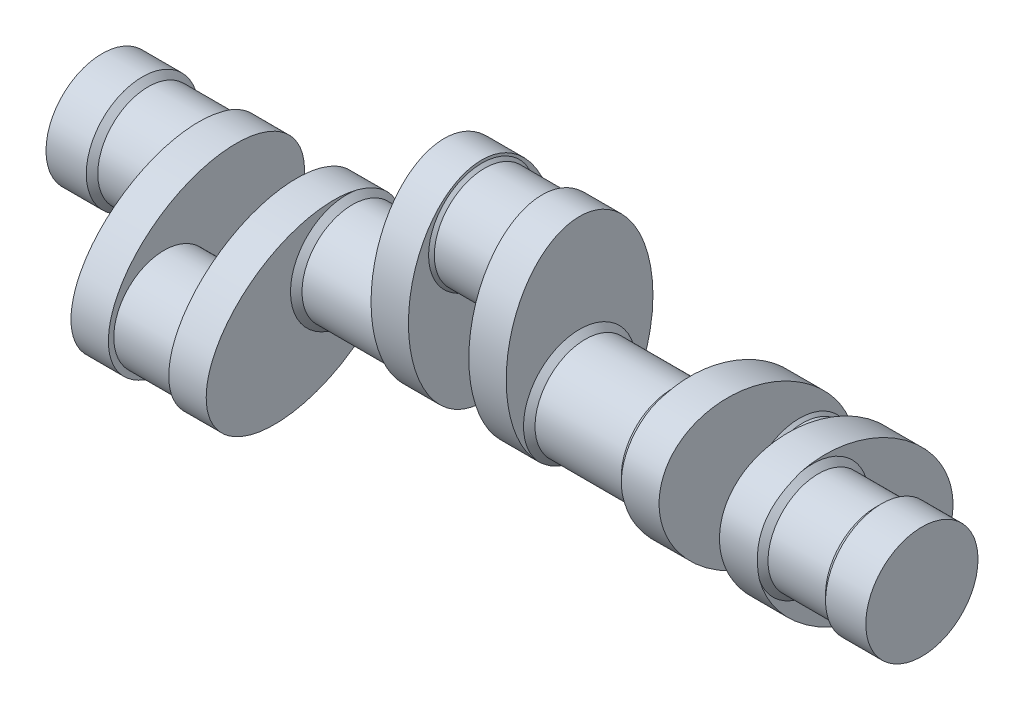
SolidWorks part; units mm, degrees
material "AISI 304"
ref_plane "Front Plane" through (0, 0, 0) normal (0, 0, 1) x (1, 0, 0)
ref_plane "Top Plane" through (0, 0, 0) normal (0, 1, 0) x (1, 0, 0)
ref_plane "Right Plane" through (0, 0, 0) normal (1, 0, 0) x (0, 0, -1)
sketch "Sketch1" plane through (0, 0, 0) normal (1, 0, 0) x (0, 0, -1)
  line L0 (0, 0) -> (0, -17) construction
  ellipse E0 centre (0, -17) end of major axis (0, -53.5) minor radius 25.5
extrude "Boss-Extrude1" add sketch "Sketch1" along normal blind 13
sketch "Sketch2" plane through (13, 0, 0) normal (1, 0, 0) x (0, 0, -1)
  circle A0 centre (0, 0) radius 17.5
  dimension "D1" = 35
extrude "Boss-Extrude2" add sketch "Sketch2" along normal blind 21
chamfer "Chamfer1" distance 1 angle 45 1 edges at (13, 0, -17.5)
sketch "Sketch3" plane through (34, 0, 0) normal (1, 0, 0) x (0, 0, -1)
  line L0 (0, 0) -> (0, -17) construction
  ellipse E0 centre (0, -17) end of major axis (0, -53.5) minor radius 25.5
extrude "Boss-Extrude3" add sketch "Sketch3" along normal blind 13
chamfer "Chamfer2" distance 1 angle 45 1 edges at (34, 0, -17.5)
sketch "Sketch5" plane through (47, 0, 0) normal (1, 0, 0) x (0, 0, -1)
  line L0 (0, 0) -> (0, -34) construction
  circle A0 centre (0, -34) radius 17.5
extrude "Boss-Extrude4" add sketch "Sketch5" along normal blind 34
chamfer "Chamfer3" distance 2 angle 45 1 edges at (47, -34, -17.5)
sketch "Sketch6" plane through (81, 0, 0) normal (1, 0, 0) x (0, 0, -1)
  line L0 (0, -34) -> (14.7224, -42.5) construction
  line L1 (0, -34) -> (0, 0) construction
  line L2 (27.4724, -20.4164) -> (14.7224, -42.5) construction
  ellipse E0 centre (14.7224, -42.5) end of major axis (46.3324, -60.75) minor radius 25.5
  dimension "D1" = 17
  dimension "D2" = 120
  dimension "D3" = 25.5
  dimension "D4" = 36.5
extrude "Boss-Extrude5" add sketch "Sketch6" along normal blind 13
chamfer "Chamfer4" distance 2 angle 45 1 edges at (81, -34, -17.5)
sketch "Sketch7" plane through (94, 0, 0) normal (1, 0, 0) x (0, 0, -1)
  line L0 (0, 0) -> (0, -34) construction
  line L1 (0, -34) -> (29.4449, -51) construction
  circle A0 centre (29.4449, -51) radius 17.5
  dimension "D1" = 120
  dimension "D2" = 34
extrude "Boss-Extrude6" add sketch "Sketch7" along normal blind 21
chamfer "Chamfer5" distance 1 angle 45 1 edges at (94, -51, -46.9449)
sketch "Sketch8" plane through (115, 0, 0) normal (1, 0, 0) x (0, 0, -1)
  line L0 (29.4449, -51) -> (14.7224, -42.5) construction
  line L1 (29.4449, -51) -> (29.4449, -68) construction
  line L2 (14.7224, -42.5) -> (1.9724, -64.5836) construction
  line L3 (14.7224, -42.5) -> (-16.8875, -24.25) construction
  ellipse E0 centre (14.7224, -42.5) end of major axis (-16.8875, -24.25) minor radius 25.5
  dimension "D1" = 120
  dimension "D2" = 25.5
  dimension "D3" = 17
  dimension "D4" = 36.5
extrude "Boss-Extrude7" add sketch "Sketch8" along normal blind 13
chamfer "Chamfer6" distance 1 angle 45 1 edges at (115, -51, -46.9449)
sketch "Sketch9" plane through (128, 0, 0) normal (1, 0, 0) x (0, 0, -1)
  line L0 (0, 0) -> (0, -34) construction
  circle A0 centre (0, -34) radius 17.5
  dimension "D1" = 35
  dimension "D2" = 34
extrude "Boss-Extrude8" add sketch "Sketch9" along normal blind 24
sketch "Sketch10" plane through (152, 0, 0) normal (1, 0, 0) x (0, 0, -1)
  circle A0 centre (0, -34) radius 19.5
  dimension "D1" = 39
extrude "Boss-Extrude9" add sketch "Sketch10" along normal blind 14
chamfer "Chamfer7" distance 2 angle 45 1 edges at (128, -34, -17.5)
chamfer "Chamfer8" distance 2 angle 45 1 edges at (152, -34, -17.5)
sketch "Sketch11" plane through (0, 0, 0) normal (-1, 0, 0) x (0, 0, 1)
  line L0 (0, 0) -> (0, -34) construction
  circle A0 centre (0, -34) radius 17.5
  dimension "D2" = 35
  dimension "D1" = 34
extrude "Boss-Extrude10" add sketch "Sketch11" along normal blind 34
chamfer "Chamfer9" distance 2 angle 45 1 edges at (0, -34, -17.5)
sketch "Sketch12" plane through (-34, 0, 0) normal (-1, 0, 0) x (0, 0, 1)
  line L0 (0, 0) -> (0, -34) construction
  line L1 (0, -34) -> (14.7224, -42.5) construction
  line L2 (14.7224, -42.5) -> (27.4724, -20.4164) construction
  line L3 (14.7224, -42.5) -> (46.3324, -60.75) construction
  ellipse E0 centre (14.7224, -42.5) end of major axis (-16.8875, -24.25) minor radius 25.5
  dimension "D1" = 34
  dimension "D2" = 120
  dimension "D3" = 17
  dimension "D4" = 36.5
  dimension "D5" = 25.5
extrude "Boss-Extrude11" add sketch "Sketch12" along normal blind 13
chamfer "Chamfer10" distance 2 angle 45 1 edges at (-34, -34, 17.5)
sketch "Sketch13" plane through (-47, 0, 0) normal (-1, 0, 0) x (0, 0, 1)
  line L0 (0, -34) -> (29.4449, -51) construction
  line L3 (0, 0) -> (0, -34) construction
  circle A0 centre (29.4449, -51) radius 17.5
  dimension "D4" = 35
  dimension "D1" = 120
  dimension "D2" = 34
  dimension "D3" = 34
extrude "Boss-Extrude12" add sketch "Sketch13" along normal blind 21
chamfer "Chamfer11" distance 1 angle 45 1 edges at (-47, -51, 46.9449)
sketch "Sketch15" plane through (-68, 0, 0) normal (-1, 0, 0) x (0, 0, 1)
  line L0 (0, 0) -> (0, -34) construction
  line L1 (0, -34) -> (14.7224, -42.5) construction
  line L2 (14.7224, -42.5) -> (27.4724, -20.4164) construction
  line L3 (14.7224, -42.5) -> (46.3324, -60.75) construction
  ellipse E0 centre (14.7224, -42.5) end of major axis (-16.8875, -24.25) minor radius 25.5
  dimension "D1" = 120
  dimension "D2" = 17
  dimension "D3" = 34
  dimension "D4" = 90
  dimension "D5" = 36.5
  dimension "D6" = 25.5
  dimension "D7" = 36.5
extrude "Boss-Extrude13" add sketch "Sketch15" along normal blind 13
sketch "Sketch16" plane through (-81, 0, 0) normal (-1, 0, 0) x (0, 0, 1)
  line L0 (0, 0) -> (0, -34) construction
  circle A0 centre (0, -34) radius 17.5
  dimension "D1" = 35
  dimension "D2" = 34
extrude "Boss-Extrude14" add sketch "Sketch16" along normal blind 24 contours A0
sketch "Sketch17" plane through (-105, 0, 0) normal (-1, 0, 0) x (0, 0, 1)
  circle A0 centre (0, -34) radius 19.5
  dimension "D1" = 39
extrude "Boss-Extrude15" add sketch "Sketch17" along normal blind 14 contours A0
chamfer "Chamfer12" distance 2 angle 45 1 edges at (-105, -34, 17.5)
chamfer "Chamfer13" distance 2 angle 45 1 edges at (-81, -34, 17.5)
